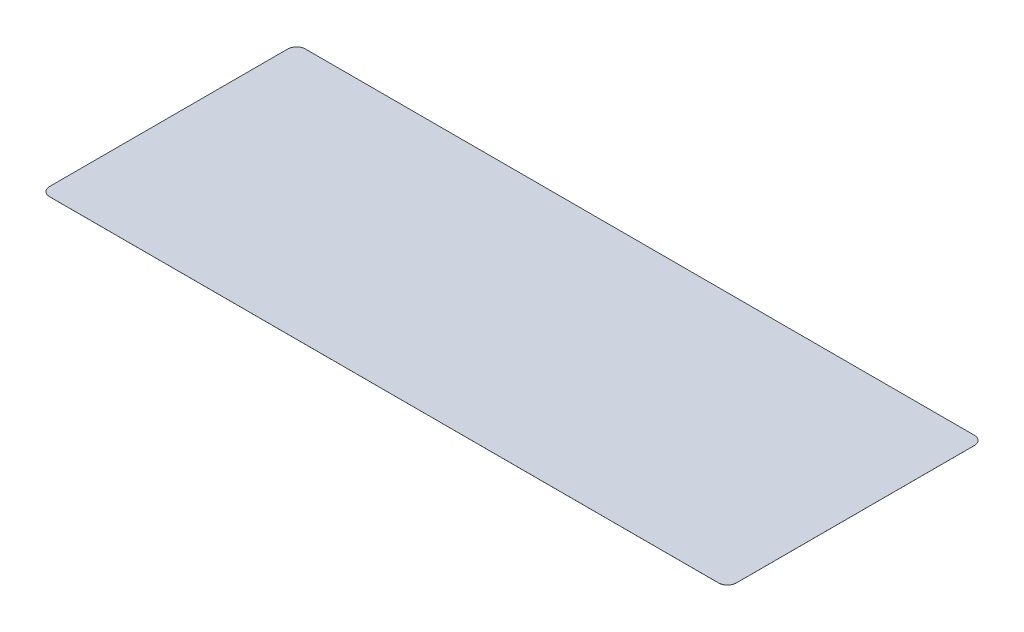
SolidWorks part; units mm, degrees
material "ETFE Film"
ref_plane "Front Plane" through (0, 0, 0) normal (0, 0, 1) x (1, 0, 0)
ref_plane "Top Plane" through (0, 0, 0) normal (0, 1, 0) x (1, 0, 0)
ref_plane "Right Plane" through (0, 0, 0) normal (1, 0, 0) x (0, 0, -1)
ref_axis "Axis1" through (0, -55, 0) along (0, 1, 0)
sketch "Sketch1" plane through (0, 0, 0) normal (0, 1, 0) x (1, 0, 0)
  line L8 (946.15, -361.95) -> (-946.15, -361.95) construction
  line L9 (-971.55, -336.55) -> (-971.55, 336.55) construction
  line L10 (-946.15, 361.95) -> (946.15, 361.95) construction
  line L11 (971.55, 336.55) -> (971.55, -336.55) construction
  line L12 (946.15, -361.95) -> (-946.15, -361.95)
  line L13 (-971.55, -336.55) -> (-971.55, 336.55)
  line L14 (-946.15, 361.95) -> (946.15, 361.95)
  line L15 (971.55, 336.55) -> (971.55, -336.55)
  arc A8 (946.15, -361.95) -> (971.55, -336.55) centre (946.15, -336.55) ccw construction
  arc A9 (-971.55, -336.55) -> (-946.15, -361.95) centre (-946.15, -336.55) ccw construction
  arc A10 (-946.15, 361.95) -> (-971.55, 336.55) centre (-946.15, 336.55) ccw construction
  arc A11 (971.55, 336.55) -> (946.15, 361.95) centre (946.15, 336.55) ccw construction
  arc A12 (946.15, -361.95) -> (971.55, -336.55) centre (946.15, -336.55) ccw
  arc A13 (-971.55, -336.55) -> (-946.15, -361.95) centre (-946.15, -336.55) ccw
  arc A14 (-946.15, 361.95) -> (-971.55, 336.55) centre (-946.15, 336.55) ccw
  arc A15 (971.55, 336.55) -> (946.15, 361.95) centre (946.15, 336.55) ccw
extrude "Boss-Extrude1" add sketch "Sketch1" along normal blind 0.127
